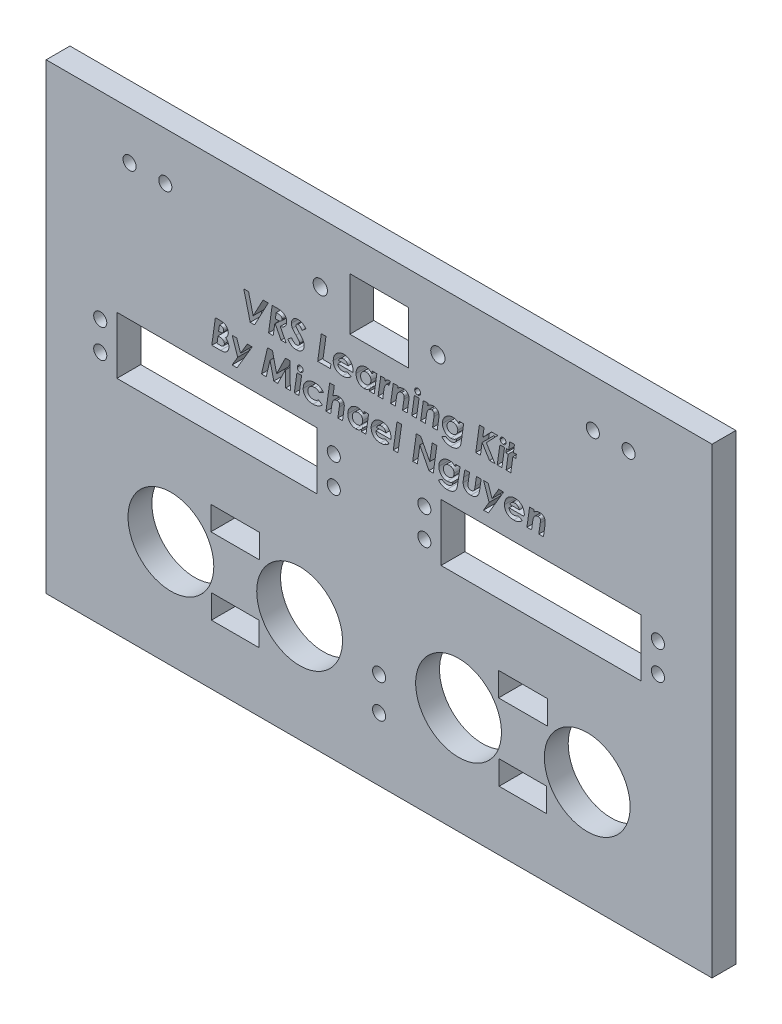
SolidWorks part; units mm, degrees
ref_plane "Front Plane" through (0, 0, 0) normal (0, 0, 1) x (1, 0, 0)
ref_plane "Top Plane" through (0, 0, 0) normal (0, 1, 0) x (1, 0, 0)
ref_plane "Right Plane" through (0, 0, 0) normal (1, 0, 0) x (0, 0, -1)
sketch "Sketch1" plane through (0, 0, 0) normal (0, 1, 0) x (1, 0, 0)
  line L1 (0, 0) -> (144.7, 0)
  line L2 (0, 0) -> (0, 5)
  line L3 (0, 5) -> (144.7, 5)
  line L4 (144.7, 0) -> (144.7, 5)
  dimension "D1" = 5
  dimension "D2" = 144.7
extrude "rearWall" add sketch "Sketch1" along normal blind 96.9847
ref_plane "referencePlane1" through (0, 91.9847, 0) normal (0, 1, 0) x (1, 0, 0)
sketch "Sketch12" plane through (0, 91.9847, 0) normal (0, 1, 0) x (1, 0, 0)
  line L0 (0, 0) -> (144.7, 0) construction
  line L1 (102.85, 0) -> (41.85, 0)
  line L2 (102.85, 0) -> (102.85, -24.75)
  line L3 (102.85, -24.75) -> (41.85, -24.75)
  line L4 (41.85, 0) -> (41.85, -24.75)
  point P4 (72.35, 0)
  point P7 (72.35, 0)
  dimension "D1" = 61
  dimension "D2" = 24.75
extrude "usbBracketBase" add sketch "Sketch12" against normal blind 16.75
sketch "Sketch13" plane through (0, 0, 24.75) normal (0, 0, 1) x (1, 0, 0)
  line L0 (72.35, 75.2347) -> (72.35, 91.9847) construction
  line L1 (41.85, 75.2347) -> (102.85, 75.2347) construction
  line L2 (20.7161, 91.9847) -> (-20.7161, 91.9847) construction
  line L3 (41.85, 75.2347) -> (41.85, 91.9847) construction
  line L4 (41.85, 90.2347) -> (49.85, 90.2347)
  line L5 (41.85, 90.2347) -> (41.85, 75.2347)
  line L6 (41.85, 75.2347) -> (49.85, 75.2347)
  line L7 (49.85, 90.2347) -> (49.85, 75.2347)
  line L8 (102.85, 75.2347) -> (94.85, 75.2347)
  line L9 (94.85, 90.2347) -> (94.85, 75.2347)
  line L10 (102.85, 90.2347) -> (94.85, 90.2347)
  line L11 (102.85, 90.2347) -> (102.85, 75.2347)
  dimension "D1" = 15
  dimension "D2" = 8
extrude "usbBracketTabs" cut sketch "Sketch13" against normal up to surface (24.75 mm away) up to face at (72.35, 83.6097, 0)
sketch "Sketch16" plane through (0, 0, 24.75) normal (0, 0, 1) x (1, 0, 0)
  line L0 (41.85, 91.9847) -> (102.85, 91.9847) construction
  line L1 (51.6, 76.9847) -> (93.1, 76.9847)
  line L2 (51.6, 76.9847) -> (51.6, 91.9847)
  line L3 (51.6, 91.9847) -> (93.1, 91.9847)
  line L4 (93.1, 76.9847) -> (93.1, 91.9847)
  point P4 (72.35, 91.9847)
  point P7 (72.35, 91.9847)
  dimension "D1" = 41.5
  dimension "D2" = 15
extrude "usbCavity" cut sketch "Sketch16" against normal up to surface (24.75 mm away) up to face at (72.35, 86.9222, 0)
sketch "Sketch17" plane through (0, 91.9847, 0) normal (0, 1, 0) x (1, 0, 0)
  line L0 (72.35, -24.75) -> (72.35, 0) construction
  line L1 (51.6, -24.75) -> (93.1, -24.75) construction
  line L2 (102.85, -12.375) -> (41.85, -12.375) construction
  line L3 (102.85, -24.75) -> (102.85, 0) construction
  line L4 (41.85, 0) -> (41.85, -24.75) construction
  line L5 (0, 0) -> (144.7, 0) construction
  line L6 (93.1, -24.75) -> (102.85, -24.75) construction
  circle A0 centre (98.85, -21.625) radius 1.375
  circle A1 centre (98.85, -3.125) radius 1.375
  circle A2 centre (45.85, -3.125) radius 1.375
  circle A3 centre (45.85, -21.625) radius 1.375
  dimension "D1" = 2.75
  dimension "D2" = 3.125
  dimension "D3" = 4
extrude "usbTopChassisMountingHoles" cut sketch "Sketch17" against normal blind 1.75
sketch "Sketch18" plane through (0, 0, 0) normal (0, 0, 1) x (1, 0, 0)
  line L0 (72.35, 76.9847) -> (72.35, 96.9847) construction
  line L1 (51.6, 76.9847) -> (93.1, 76.9847) construction
  line L2 (0, 96.9847) -> (144.7, 96.9847) construction
  line L3 (51.6, 91.9847) -> (51.6, 76.9847) construction
  circle A0 centre (60.015, 84.4847) radius 1.5
  circle A1 centre (84.685, 84.4847) radius 1.5
  dimension "D1" = 3
  dimension "D2" = 7.5
  dimension "D3" = 8.415
extrude "usbMountingHoles" cut sketch "Sketch18" against normal through all
sketch "Sketch19" plane through (0, 0, 0) normal (0, 0, 1) x (1, 0, 0)
  line L0 (72.35, 76.9847) -> (72.35, 78.9847) construction
  line L1 (66.225, 78.9847) -> (78.475, 78.9847)
  line L2 (66.225, 78.9847) -> (66.225, 89.9847)
  line L3 (66.225, 89.9847) -> (78.475, 89.9847)
  line L4 (78.475, 78.9847) -> (78.475, 89.9847)
  line L7 (51.6, 76.9847) -> (93.1, 76.9847) construction
  point P8 (72.35, 78.9847)
  dimension "D1" = 12.25
  dimension "D2" = 11
  dimension "D3" = 2
extrude "usbPortHole" cut sketch "Sketch19" against normal through all
sketch "Sketch20" plane through (0, 91.9847, 0) normal (0, 1, 0) x (1, 0, 0)
  line L0 (0, 0) -> (144.7, 0) construction
  line L5 (129.7, 0) -> (142.2, 0)
  line L6 (129.7, 0) -> (129.7, -17.135)
  line L7 (129.7, -17.135) -> (142.2, -17.135)
  line L8 (142.2, 0) -> (142.2, -17.135)
  line L9 (72.35, 5) -> (72.35, -24.75) construction
  line L10 (144.7, 5) -> (0, 5) construction
  line L11 (51.6, -24.75) -> (93.1, -24.75) construction
  line L12 (15, -17.135) -> (2.5, -17.135)
  line L13 (2.5, 0) -> (2.5, -17.135)
  line L14 (15, 0) -> (2.5, 0)
  line L15 (15, 0) -> (15, -17.135)
  dimension "D1" = 2.5
  dimension "D2" = 12.5
  dimension "D3" = 17.135
extrude "topChassisMountingTabs" add sketch "Sketch20" against normal blind 5
sketch "Sketch21" plane through (0, 91.9847, 0) normal (0, 1, 0) x (1, 0, 0)
  line L0 (142.2, -17.135) -> (142.2, 0) construction
  line L1 (142.2, 0) -> (129.7, 0) construction
  line L2 (72.35, 5) -> (72.35, -24.75) construction
  line L3 (144.7, 5) -> (0, 5) construction
  line L4 (51.6, -24.75) -> (93.1, -24.75) construction
  circle A0 centre (135.95, -8.5675) radius 1.375
  circle A1 centre (8.75, -8.5675) radius 1.375
  dimension "D1" = 2.75
  dimension "D2" = 6.25
  dimension "D3" = 8.5675
extrude "topChassisMountingHoles" cut sketch "Sketch21" against normal blind 5
ref_plane "referencePlane2" through (0, 7.5, 0) normal (0, -1, 0) x (-1, 0, 0)
sketch "bottomChassisReference" plane through (0, 0, -5) normal (0, 0, -1) x (-1, 0, 0)
  line L0 (-144.7, 0) -> (0, 0) construction
  line L1 (-142.2, 0) -> (-2.5, 0) construction
  line L2 (-142.2, 0) -> (-142.2, 7.5) construction
  line L3 (-142.2, 7.5) -> (-2.5, 7.5) construction
  line L4 (-2.5, 0) -> (-2.5, 7.5) construction
  point P6 (-72.35, 0)
  point P7 (-72.35, 0)
  dimension "D1" = 7.5
  dimension "D2" = 139.7
sketch "Sketch23" plane through (0, 7.5, 0) normal (0, -1, 0) x (-1, 0, 0)
  line L0 (-72.35, 0) -> (-72.35, -12.5) construction
  line L1 (0, 0) -> (-144.7, 0) construction
  line L3 (-15, 0) -> (-65, 0)
  line L4 (-15, 0) -> (-15, -12.5)
  line L5 (-15, -12.5) -> (-65, -12.5)
  line L6 (-65, 0) -> (-65, -12.5)
  line L7 (-129.7, -12.5) -> (-79.7, -12.5)
  line L8 (-79.7, 0) -> (-79.7, -12.5)
  line L9 (-129.7, 0) -> (-79.7, 0)
  line L10 (-129.7, 0) -> (-129.7, -12.5)
  dimension "D1" = 50
  dimension "D2" = 12.5
  dimension "D3" = 7.35
extrude "bottomChassisMountingTabs" add sketch "Sketch23" against normal blind 1.75
sketch "Sketch24" plane through (0, 7.5, 0) normal (0, -1, 0) x (1, 0, 0)
  line L0 (72.35, 0) -> (72.35, 12.5) construction
  line L1 (94.85, 0) -> (49.85, 0) construction
  line L2 (40, 0) -> (40, 12.5) construction
  line L3 (15, 0) -> (65, 0) construction
  line L4 (65, 12.5) -> (15, 12.5) construction
  line L5 (104.7, 12.5) -> (104.7, 0) construction
  line L6 (129.7, 12.5) -> (79.7, 12.5) construction
  line L7 (79.7, 0) -> (129.7, 0) construction
  line L8 (15, 12.5) -> (15, 0) construction
  circle A0 centre (18, 9.75) radius 1.375
  circle A1 centre (62, 9.75) radius 1.375
  circle A2 centre (126.7, 9.75) radius 1.375
  circle A3 centre (82.7, 9.75) radius 1.375
  dimension "D1" = 2.75
  dimension "D2" = 3
  dimension "D3" = 2.75
extrude "bottomChassisMountingHoles" cut sketch "Sketch24" against normal blind 10
sketch "Sketch25" plane through (0, 0, 0) normal (0, 0, 1) x (1, 0, 0)
  line L0 (72.35, 96.9847) -> (72.35, 0) construction
  line L1 (15, 9.25) -> (65, 9.25) construction
  line L2 (15, 9.25) -> (15, 37) construction
  line L3 (15, 37) -> (65, 37) construction
  line L4 (65, 9.25) -> (65, 37) construction
  line L5 (0, 96.9847) -> (144.7, 96.9847) construction
  line L6 (142.2, 0) -> (2.5, 0) construction
  line L7 (40, 9.25) -> (40, 37) construction
  line L8 (15, 23.125) -> (65, 23.125) construction
  circle A0 centre (26.5, 22.5) radius 9
  circle A1 centre (18.6693, 31.289) radius 0.875
  circle A3 centre (53.5, 22.5) radius 9
  circle A4 centre (61.3307, 31.289) radius 0.875
  circle A6 centre (18.6693, 13.711) radius 0.875
  circle A7 centre (61.3307, 13.711) radius 0.875
  circle A8 centre (126.0307, 31.289) radius 0.875
  circle A9 centre (126.0307, 13.711) radius 0.875
  circle A10 centre (83.3693, 13.711) radius 0.875
  circle A11 centre (83.3693, 31.289) radius 0.875
  circle A12 centre (91.2, 22.5) radius 9
  circle A13 centre (118.2, 22.5) radius 9
  dimension "D2" = 18
  dimension "D5" = 1.75
  dimension "D9" = 3.6693
  dimension "D1" = 27.75
  dimension "D3" = 13.25
  dimension "D4" = 11.5
  dimension "D6" = 5.711
  dimension "D7" = 3.6693
  dimension "D8" = 4.461
extrude "distanceSensorMountingHoles" cut sketch "Sketch25" against normal blind 10
sketch "Sketch26" plane through (0, 0, -5) normal (0, 0, -1) x (-1, 0, 0)
  line L0 (-72.35, 0) -> (-72.35, 96.9847) construction
  line L1 (-142.2, 0) -> (-2.5, 0) construction
  line L2 (-144.7, 96.9847) -> (0, 96.9847) construction
  line L3 (-144.7, 48.4923) -> (0, 48.4923) construction
  line L4 (-144.7, 96.9847) -> (-144.7, 0) construction
  line L5 (0, 96.9847) -> (0, 0) construction
  line L6 (-54.0762, 48.5554) -> (-26.8869, 61.234) construction
  line L11 (-26.8869, 61.234) -> (-22.6608, 52.1709) construction
  line L12 (-22.6608, 52.1709) -> (-49.85, 39.4923) construction
  line L13 (-49.85, 39.4923) -> (-54.0762, 48.5554) construction
  line L14 (-51.9631, 44.0239) -> (-24.7739, 56.7024) construction
  line L15 (-46.5252, 46.5596) -> (-43.9895, 41.1217) construction
  line L16 (-41.0874, 49.0953) -> (-38.5517, 43.6574) construction
  line L17 (-35.6496, 51.631) -> (-33.1138, 46.1931) construction
  line L18 (-30.2117, 54.1667) -> (-27.676, 48.7289) construction
  line L19 (-47.062, 47.7106) -> (-45.9885, 45.4086) construction
  line L20 (-45.2574, 43.8407) -> (-37.2036, 47.5962) construction
  line L21 (-23.3228, 60.6892) -> (-50.512, 48.0106) construction
  line L22 (-50.512, 48.0106) -> (-45.4406, 37.135) construction
  line L23 (-23.3228, 60.6892) -> (-18.2514, 49.8135) construction
  line L24 (-45.4406, 37.135) -> (-18.2514, 49.8135) construction
  line L25 (-40.0028, 39.6707) -> (-45.0742, 50.5464) construction
  line L26 (-23.3228, 60.6892) -> (-17.8849, 63.2249) construction
  line L27 (-17.8849, 63.2249) -> (-12.8135, 52.3492) construction
  line L28 (-18.2514, 49.8135) -> (-12.8135, 52.3492) construction
  line L29 (-45.4406, 37.135) -> (-50.8785, 34.5992) construction
  line L30 (-50.8785, 34.5992) -> (-55.9499, 45.4749) construction
  line L31 (-50.512, 48.0106) -> (-55.9499, 45.4749) construction
  circle A0 centre (-46.5252, 46.5596) radius 3 construction
  circle A1 centre (-41.0874, 49.0953) radius 3 construction
  circle A2 centre (-35.6496, 51.631) radius 3 construction
  circle A3 centre (-30.2117, 54.1667) radius 3 construction
  circle A4 centre (-43.9895, 41.1217) radius 3 construction
  circle A5 centre (-38.5517, 43.6574) radius 3 construction
  circle A6 centre (-33.1138, 46.1931) radius 3 construction
  circle A7 centre (-27.676, 48.7289) radius 3 construction
  circle A8 centre (-47.062, 47.7106) radius 0.575
  circle A9 centre (-45.9885, 45.4086) radius 0.575
  circle A10 centre (-41.6692, 50.3408) radius 0.575
  circle A11 centre (-40.5958, 48.0388) radius 0.575
  circle A12 centre (-36.2764, 52.971) radius 0.575
  circle A13 centre (-35.203, 50.669) radius 0.575
  circle A14 centre (-30.8837, 55.6013) radius 0.575
  circle A15 centre (-29.8102, 53.2992) radius 0.575
  circle A16 centre (-27.009, 47.292) radius 0.575
  circle A17 centre (-28.0824, 49.594) radius 0.575
  circle A18 centre (-33.5637, 47.1536) radius 0.575
  circle A19 centre (-32.4903, 44.8516) radius 0.575
  circle A20 centre (-37.9715, 42.4111) radius 0.575
  circle A21 centre (-39.045, 44.7132) radius 0.575
  circle A22 centre (-44.5263, 42.2727) radius 0.575
  circle A23 centre (-43.4528, 39.9707) radius 0.575
  circle A24 centre (-101.2472, 39.9707) radius 0.575
  circle A25 centre (-100.1737, 42.2727) radius 0.575
  circle A26 centre (-106.7285, 42.4111) radius 0.575
  circle A27 centre (-105.655, 44.7132) radius 0.575
  circle A28 centre (-112.2097, 44.8516) radius 0.575
  circle A29 centre (-111.1363, 47.1536) radius 0.575
  circle A30 centre (-117.691, 47.292) radius 0.575
  circle A31 centre (-116.6176, 49.594) radius 0.575
  circle A32 centre (-113.8163, 55.6013) radius 0.575
  circle A33 centre (-114.8898, 53.2992) radius 0.575
  circle A34 centre (-109.497, 50.669) radius 0.575
  circle A35 centre (-108.4236, 52.971) radius 0.575
  circle A36 centre (-103.0308, 50.3408) radius 0.575
  circle A37 centre (-104.1042, 48.0388) radius 0.575
  circle A38 centre (-98.7115, 45.4086) radius 0.575
  circle A39 centre (-97.638, 47.7106) radius 0.575
  circle A40 centre (-25.4458, 58.137) radius 0.575
  circle A41 centre (-24.3724, 55.835) radius 0.575
  circle A42 centre (-22.6446, 52.1297) radius 0.575
  circle A43 centre (-21.5711, 49.8277) radius 0.575
  circle A44 centre (-20.008, 60.6727) radius 0.575
  circle A45 centre (-18.9345, 58.3707) radius 0.575
  circle A46 centre (-17.2067, 54.6654) radius 0.575
  circle A47 centre (-16.1333, 52.3634) radius 0.575
  circle A56 centre (-128.5667, 52.3634) radius 0.575
  circle A57 centre (-124.692, 60.6727) radius 0.575
  circle A58 centre (-125.7655, 58.3707) radius 0.575
  circle A59 centre (-127.4933, 54.6654) radius 0.575
  circle A60 centre (-123.1289, 49.8277) radius 0.575
  circle A61 centre (-122.0554, 52.1297) radius 0.575
  circle A62 centre (-120.3276, 55.835) radius 0.575
  circle A63 centre (-119.2542, 58.137) radius 0.575
  circle A64 centre (-14.5701, 63.2084) radius 0.575 [skipped]
  circle A65 centre (-13.4967, 60.9064) radius 0.575 [skipped]
  circle A66 centre (-11.7689, 57.2011) radius 0.575 [skipped]
  circle A67 centre (-10.6955, 54.8991) radius 0.575 [skipped]
  circle A68 centre (-52.5515, 45.2887) radius 0.575
  circle A69 centre (-51.3724, 42.7601) radius 0.575
  circle A70 centre (-50.0169, 39.8503) radius 0.575
  circle A71 centre (-48.8366, 37.3223) radius 0.575
  circle A72 centre (-95.8634, 37.3223) radius 0.575
  circle A73 centre (-94.6831, 39.8503) radius 0.575
  circle A74 centre (-93.3276, 42.7601) radius 0.575
  circle A75 centre (-92.1485, 45.2887) radius 0.575
  circle A76 centre (-24.7739, 56.7024) radius 3 construction
  point P41 (-46.5252, 46.5596)
  dimension "D2" = 6
  dimension "D12" = 1.15
  dimension "D1" = 25
  dimension "D4" = 6
  dimension "D5" = 6
  dimension "D6" = 10
  dimension "D7" = 9
  dimension "D8" = 22.5
  dimension "D9" = 6
  dimension "D10" = 30
  dimension "D11" = 2.54
  dimension "D14" = 4
  dimension "D15" = 1.395
  dimension "D16" = 6
  dimension "D17" = 0.395
  dimension "D18" = 2.395
  dimension "D19" = 6
  dimension "D20" = 6
  dimension "D21" = 6
  dimension "D3" = 4
  dimension "D13" = 4
sketch "Sketch28" plane through (144.7, 0, 0) normal (1, 0, 0) x (0, 0, -1)
  line L4 (0, 0) -> (5, 0)
  line L5 (5, 0) -> (5, 96.9847)
  line L6 (5, 96.9847) -> (0, 96.9847)
  line L7 (0, 96.9847) -> (0, 0)
  line L8 (0, 0) -> (5, 0)
  line L9 (5, 0) -> (5, 96.9847)
  line L10 (5, 96.9847) -> (0, 96.9847)
  line L11 (0, 96.9847) -> (0, 0)
  dimension "D1" = 0
extrude "Boss-Extrude2" add sketch "Sketch28" along normal blind 2.5
sketch "Sketch29" plane through (0, 0, -5) normal (0, 0, -1) x (-1, 0, 0)
  line L0 (-72.35, 96.9847) -> (-72.35, 0) construction
  line L3 (-118.2, 22.5) -> (-109.2, 22.5) construction
  line L4 (-109.81, 28.5) -> (-99.59, 28.5)
  line L5 (-109.81, 28.5) -> (-109.81, 33.5)
  line L6 (-109.81, 33.5) -> (-99.59, 33.5)
  line L7 (-99.59, 28.5) -> (-99.59, 33.5)
  line L8 (-118.2, 22.5) -> (-118.2, 31.5) construction
  line L10 (-109.7, 12.5) -> (-99.7, 12.5)
  line L11 (-109.7, 12.5) -> (-109.7, 17.5)
  line L12 (-109.7, 17.5) -> (-99.7, 17.5)
  line L13 (-99.7, 12.5) -> (-99.7, 17.5)
  line L23 (-78.475, 89.9847) -> (-66.225, 89.9847) construction
  line L24 (-147.2, 96.9847) -> (0, 96.9847) construction
  line L25 (-147.2, 0) -> (0, 0) construction
  line L26 (-45, 12.5) -> (-45, 17.5)
  line L27 (-35, 12.5) -> (-45, 12.5)
  line L28 (-35, 12.5) -> (-35, 17.5)
  line L29 (-35, 17.5) -> (-45, 17.5)
  line L30 (-34.89, 28.5) -> (-34.89, 33.5)
  line L31 (-34.89, 28.5) -> (-45.11, 28.5)
  line L32 (-45.11, 28.5) -> (-45.11, 33.5)
  line L33 (-34.89, 33.5) -> (-45.11, 33.5)
  circle A0 centre (-118.2, 22.5) radius 9 construction
  circle A1 centre (-118.2, 22.5) radius 9 construction
  point P5 (-72.35, 89.9847)
  point P13 (-109.81, 31)
  point P20 (-109.7, 15)
  dimension "D1" = 5
  dimension "D2" = 10.22
  dimension "D3" = 8.5
  dimension "D4" = 8.39
  dimension "D5" = 10
  dimension "D6" = 5
  dimension "D7" = 5
  dimension "D8" = 8.5
extrude "Cut-Extrude1" cut sketch "Sketch29" against normal blind 10
sketch "Sketch30" plane through (0, 0, -5) normal (0, 0, -1) x (-1, 0, 0)
  line L0 (-73.6, 0) -> (-73.6, 96.9847) construction
  line L1 (-147.2, 0) -> (0, 0) construction
  line L2 (-147.2, 96.9847) -> (0, 96.9847) construction
  line L3 (-147.2, 0) -> (-73.6, 0) construction
  line L4 (-132.2, 42.4985) -> (-90.2, 42.4985)
  line L5 (-132.2, 42.4985) -> (-132.2, 54.4985)
  line L6 (-132.2, 54.4985) -> (-90.2, 54.4985)
  line L7 (-90.2, 42.4985) -> (-90.2, 54.4985)
  line L8 (-147.2, 0) -> (-147.2, 96.9847) construction
  line L9 (-99.59, 33.5) -> (-109.81, 33.5) construction
  line L10 (-15, 54.4985) -> (-57, 54.4985)
  line L11 (-57, 42.4985) -> (-57, 54.4985)
  line L12 (-15, 42.4985) -> (-57, 42.4985)
  line L13 (-15, 42.4985) -> (-15, 54.4985)
  dimension "D1" = 42
  dimension "D2" = 12
  dimension "D3" = 15
  dimension "D4" = 8.9985
extrude "Cut-Extrude2" cut sketch "Sketch30" against normal blind 10
sketch "Sketch31" plane through (0, 0, -5) normal (0, 0, -1) x (-1, 0, 0)
  line L0 (-111.2, 42.4985) -> (-111.2, 54.4985) construction
  line L1 (-132.2, 42.4985) -> (-90.2, 42.4985) construction
  line L2 (-90.2, 54.4985) -> (-132.2, 54.4985) construction
  line L3 (-90.2, 54.4985) -> (-83.2, 54.4985) construction
  line L4 (-132.2, 42.4985) -> (-139.2, 42.4985) construction
  line L6 (-132.2, 54.4985) -> (-139.2, 54.4985) construction
  line L7 (-139.2, 42.4985) -> (-139.2, 54.4985) construction
  line L8 (-83.2, 42.4985) -> (-83.2, 54.4985) construction
  line L9 (-90.2, 42.4985) -> (-83.2, 42.4985) construction
  line L10 (-90.2, 42.4985) -> (-90.2, 54.4985) construction
  line L11 (-73.6, 96.9847) -> (-73.6, 0) construction
  line L12 (-147.2, 96.9847) -> (0, 96.9847) construction
  line L13 (-147.2, 0) -> (0, 0) construction
  line L14 (-57, 42.4985) -> (-57, 54.4985) construction
  line L15 (-57, 42.4985) -> (-64, 42.4985) construction
  line L16 (-64, 42.4985) -> (-64, 54.4985) construction
  line L17 (-57, 54.4985) -> (-64, 54.4985) construction
  line L18 (-15, 54.4985) -> (-8, 54.4985) construction
  line L19 (-8, 42.4985) -> (-8, 54.4985) construction
  line L20 (-15, 42.4985) -> (-8, 42.4985) construction
  line L21 (-15, 42.4985) -> (-15, 54.4985) construction
  line L22 (-139.2, 48.4985) -> (-132.2, 48.4985) construction
  line L23 (-132.2, 42.4985) -> (-132.2, 48.4985) construction
  line L24 (-132.2, 54.4985) -> (-132.2, 42.4985) construction
  line L25 (-132.2, 48.4985) -> (-132.2, 54.4985) construction
  circle A0 centre (-135.7, 51.4985) radius 1.375
  circle A1 centre (-135.7, 45.4985) radius 1.375
  circle A2 centre (-86.7, 45.4985) radius 1.375
  circle A3 centre (-86.7, 51.4985) radius 1.375
  circle A4 centre (-60.5, 45.4985) radius 1.375
  circle A5 centre (-60.5, 51.4985) radius 1.375
  circle A6 centre (-11.5, 45.4985) radius 1.375
  circle A7 centre (-11.5, 51.4985) radius 1.375
  point P35 (-132.2, 51.4985)
  point P36 (-135.7, 48.4985)
  dimension "D2" = 2.75
  dimension "D1" = 7
extrude "Cut-Extrude3" cut sketch "Sketch31" against normal blind 10
sketch "Sketch32" plane through (0, 96.9847, 0) normal (0, 1, 0) x (1, 0, 0)
  line L0 (72.35, -24.75) -> (72.35, 5) construction
  line L1 (142.2, -17.135) -> (147.2, -17.135)
  line L2 (142.2, -17.135) -> (142.2, 5)
  line L3 (142.2, 5) -> (147.2, 5)
  line L4 (147.2, -17.135) -> (147.2, 5)
  line L7 (51.6, -24.75) -> (93.1, -24.75) construction
  line L8 (147.2, 5) -> (0, 5) construction
  line L9 (2.5, 5) -> (-2.5, 5)
  line L10 (-2.5, -17.135) -> (-2.5, 5)
  line L11 (2.5, -17.135) -> (-2.5, -17.135)
  line L12 (2.5, -17.135) -> (2.5, 5)
extrude "Cut-Extrude4" cut sketch "Sketch32" against normal through all
sketch "Sketch33" plane through (0, 0, -5) normal (0, 0, -1) x (-1, 0, 0)
  line L1 (-9.1526, 60.4475) -> (-139.9259, 60.4475)
  line L2 (-9.1526, 60.4475) -> (-9.1526, 10.7226)
  line L3 (-9.1526, 10.7226) -> (-139.9259, 10.7226)
  line L4 (-139.9259, 60.4475) -> (-139.9259, 10.7226)
extrude "Boss-Extrude3" add sketch "Sketch33" against normal up to surface (5 mm away) up to face at (59.125, 45.4985, 0)
sketch "Sketch34" plane through (0, 0, 0) normal (0, 0, 1) x (1, 0, 0)
  line L0 (72.35, 96.9847) -> (72.35, 0) construction
  line L1 (2.5, 96.9847) -> (142.2, 96.9847) construction
  line L2 (2.5, 0) -> (142.2, 0) construction
  line L4 (15, 9.25) -> (65, 9.25) construction
  line L7 (104.7, 9.25) -> (104.7, 42.4985) construction
  line L8 (129.7, 9.25) -> (79.7, 9.25) construction
  line L9 (132.2, 42.4985) -> (90.2, 42.4985) construction
  line L10 (15, 9.25) -> (65, 9.25) construction
  line L11 (15, 9.25) -> (15, 37) construction
  line L12 (15, 37) -> (65, 37) construction
  line L13 (65, 9.25) -> (65, 37) construction
  line L14 (65, 9.25) -> (65, 7.5) construction
  line L15 (40, 9.25) -> (40, 37) construction
  line L16 (109.81, 33.5) -> (99.59, 33.5)
  line L17 (34.89, 28.5) -> (45.11, 28.5)
  line L18 (34.89, 28.5) -> (34.89, 33.5)
  line L19 (34.89, 33.5) -> (45.11, 33.5)
  line L20 (45.11, 28.5) -> (45.11, 33.5)
  line L21 (35, 17.5) -> (45, 17.5)
  line L22 (35, 17.5) -> (35, 12.5)
  line L23 (35, 12.5) -> (45, 12.5)
  line L24 (45, 17.5) -> (45, 12.5)
  line L25 (99.59, 28.5) -> (99.59, 33.5)
  line L26 (109.81, 28.5) -> (99.59, 28.5)
  line L27 (109.81, 28.5) -> (109.81, 33.5)
  line L28 (109.7, 12.5) -> (99.7, 12.5)
  line L29 (99.7, 17.5) -> (99.7, 12.5)
  line L30 (109.7, 17.5) -> (99.7, 17.5)
  line L31 (109.7, 17.5) -> (109.7, 12.5)
  circle A2 centre (26.5, 22.5) radius 9
  circle A3 centre (53.5, 22.5) radius 9
  circle A4 centre (18.6693, 31.289) radius 0.875
  circle A5 centre (18.6693, 13.711) radius 0.875
  circle A6 centre (61.3307, 13.711) radius 0.875
  circle A7 centre (61.3307, 31.289) radius 0.875
  circle A8 centre (83.3693, 13.711) radius 0.875
  circle A9 centre (83.3693, 31.289) radius 0.875
  circle A10 centre (91.2, 22.5) radius 9
  circle A11 centre (118.2, 22.5) radius 9
  circle A12 centre (126.0307, 13.711) radius 0.875
  circle A13 centre (126.0307, 31.289) radius 0.875
  point P38 (40, 33.5)
  point P43 (40, 17.5)
  dimension "D3" = 18
  dimension "D6" = 1.75
  dimension "D1" = 50
  dimension "D2" = 27.75
  dimension "D4" = 11.5
  dimension "D5" = 14.5
  dimension "D7" = 3.6693
  dimension "D8" = 5.711
  dimension "D9" = 4.461
  dimension "D10" = 3.6693
  dimension "D11" = 10.22
  dimension "D12" = 5
  dimension "D13" = 3.5
  dimension "D14" = 5
  dimension "D15" = 10
  dimension "D16" = 3.25
extrude "Cut-Extrude5" cut sketch "Sketch34" against normal blind 10
sketch "Sketch35" plane through (0, 0, -5) normal (0, 0, -1) x (-1, 0, 0)
  line L0 (-72.35, 0) -> (-72.35, 96.9847) construction
  line L1 (-142.2, 0) -> (-2.5, 0) construction
  line L2 (-142.2, 96.9847) -> (-2.5, 96.9847) construction
  line L3 (-59.35, 46.5252) -> (-59.35, 52.5252) construction
  line L4 (-66.35, 58.5252) -> (-10.35, 58.5252) construction
  line L5 (-66.35, 58.5252) -> (-66.35, 46.5252) construction
  line L6 (-66.35, 46.5252) -> (-10.35, 46.5252) construction
  line L7 (-10.35, 58.5252) -> (-10.35, 46.5252) construction
  line L8 (-38.35, 46.5252) -> (-38.35, 58.5252) construction
  line L9 (-59.35, 52.5252) -> (-66.35, 52.5252) construction
  line L10 (-59.35, 52.5252) -> (-59.35, 58.5252) construction
  line L12 (-85.35, 46.5252) -> (-127.35, 46.5252)
  line L13 (-59.35, 58.5252) -> (-17.35, 58.5252)
  line L14 (-59.35, 58.5252) -> (-59.35, 46.5252)
  line L15 (-59.35, 46.5252) -> (-17.35, 46.5252)
  line L16 (-17.35, 58.5252) -> (-17.35, 46.5252)
  line L17 (-127.35, 58.5252) -> (-127.35, 46.5252)
  line L18 (-85.35, 58.5252) -> (-127.35, 58.5252)
  line L19 (-85.35, 58.5252) -> (-85.35, 46.5252)
  line L20 (-85.35, 52.5252) -> (-59.35, 52.5252) construction
  circle A0 centre (-62.85, 55.5252) radius 1.375
  circle A1 centre (-62.85, 49.5252) radius 1.375
  circle A2 centre (-13.85, 49.5252) radius 1.375
  circle A3 centre (-13.85, 55.5252) radius 1.375
  circle A4 centre (-130.85, 55.5252) radius 1.375
  circle A5 centre (-130.85, 49.5252) radius 1.375
  circle A6 centre (-81.85, 49.5252) radius 1.375
  circle A7 centre (-81.85, 55.5252) radius 1.375
  point P11 (-62.85, 52.5252)
  point P19 (-59.35, 55.5252)
  point P28 (-85.35, 52.5252)
  point P44 (-72.35, 52.5252)
  dimension "D4" = 2.75
  dimension "D1" = 56
  dimension "D2" = 12
  dimension "D3" = 7
  dimension "D5" = 39.0252
  dimension "D6" = 26
  dimension "D7" = 7
extrude "Cut-Extrude6" cut sketch "Sketch35" against normal blind 10
sketch "Sketch36" plane through (0, 0, -5) normal (0, 0, -1) x (-1, 0, 0)
  line L0 (-72.35, 0) -> (-72.35, 96.9847) construction
  line L1 (-142.2, 0) -> (-2.5, 0) construction
  line L2 (-142.2, 96.9847) -> (-2.5, 96.9847) construction
  circle A0 centre (-126.0307, 31.289) radius 1.25
  circle A1 centre (-126.0307, 13.711) radius 1.25
  circle A2 centre (-83.3693, 31.289) radius 1.25
  circle A3 centre (-83.3693, 13.711) radius 1.25
  circle A4 centre (-18.6693, 13.711) radius 1.25
  circle A5 centre (-61.3307, 13.711) radius 1.25
  circle A6 centre (-61.3307, 31.289) radius 1.25
  circle A7 centre (-18.6693, 31.289) radius 1.25
  dimension "D1" = 2.5
extrude "Cut-Extrude7" cut sketch "Sketch36" against normal offset from surface (4 mm away) 1 up to face at (61.475, 55.5252, 0)
sketch "Sketch37" plane through (0, 91.9847, 0) normal (0, 1, 0) x (1, 0, 0)
  line L1 (102.85, -24.75) -> (41.85, -24.75)
  line L2 (102.85, -24.75) -> (102.85, 0)
  line L3 (102.85, 0) -> (41.85, 0)
  line L4 (41.85, -24.75) -> (41.85, 0)
extrude "Cut-Extrude8" cut sketch "Sketch37" against normal up to surface (16.75 mm away) up to face at (72.35, 75.2347, 12.375)
sketch "Sketch38" plane through (0, 91.9847, 0) normal (0, 1, 0) x (1, 0, 0)
  line L1 (142.2, -17.135) -> (2.5, -17.135)
  line L2 (142.2, -17.135) -> (142.2, 0)
  line L3 (142.2, 0) -> (2.5, 0)
  line L4 (2.5, -17.135) -> (2.5, 0)
extrude "Cut-Extrude9" cut sketch "Sketch38" against normal blind 10
sketch "Sketch39" plane through (0, 0, 0) normal (0, 0, 1) x (1, 0, 0)
  line L0 (9, 24.25) -> (15, 24.25) construction
  line L1 (65, 9.25) -> (79.7, 9.25) construction
  line L2 (65, 9.25) -> (65, 7.5) construction
  line L3 (65, 7.5) -> (79.7, 7.5) construction
  line L4 (79.7, 9.25) -> (79.7, 7.5) construction
  line L5 (69.35, 24.25) -> (75.35, 24.25) construction
  line L6 (69.35, 24.25) -> (69.35, 9.25) construction
  line L7 (69.35, 9.25) -> (75.35, 9.25) construction
  line L8 (75.35, 24.25) -> (75.35, 9.25) construction
  line L9 (9, 24.25) -> (9, 9.25) construction
  line L10 (9, 9.25) -> (15, 9.25) construction
  line L11 (15, 24.25) -> (15, 9.25) construction
  line L12 (129.7, 24.25) -> (135.7, 24.25) construction
  line L13 (129.7, 24.25) -> (129.7, 9.25) construction
  line L14 (129.7, 9.25) -> (135.7, 9.25) construction
  line L15 (135.7, 24.25) -> (135.7, 9.25) construction
  line L16 (72.35, 7.5) -> (72.35, 9.25) construction
  circle A0 centre (72.35, 20.25) radius 1.375
  circle A1 centre (72.35, 13.25) radius 1.375
  circle A2 centre (12, 20.25) radius 1.375
  circle A3 centre (12, 13.25) radius 1.375
  circle A4 centre (132.7, 13.25) radius 1.375
  circle A5 centre (132.7, 20.25) radius 1.375
  point P21 (72.35, 9.25)
  point P22 (72.35, 9.25)
  point P32 (12, 9.25)
  dimension "D3" = 2.75
  dimension "D1" = 6
  dimension "D2" = 15
  dimension "D4" = 4
  dimension "D5" = 7
extrude "Cut-Extrude10" cut sketch "Sketch39" against normal blind 10
sketch "Sketch40" plane through (0, 9.25, 0) normal (0, 1, 0) x (1, 0, 0)
  line L1 (15, -12.5) -> (129.7, -12.5)
  line L2 (15, -12.5) -> (15, 0)
  line L3 (15, 0) -> (129.7, 0)
  line L4 (129.7, -12.5) -> (129.7, 0)
extrude "Cut-Extrude11" cut sketch "Sketch40" against normal blind 10
sketch "Sketch41" plane through (0, 0, 0) normal (0, 0, 1) x (1, 0, 0)
  line L0 (2.5, 96.9847) -> (142.2, 96.9847) construction
  line L1 (2.5, 96.9847) -> (2.5, 0) construction
  line L2 (72.35, 0) -> (72.35, 96.9847) construction
  line L3 (2.5, 0) -> (142.2, 0) construction
  circle A0 centre (20, 87) radius 1.375
  circle A1 centre (27.5, 87) radius 1.375
  circle A2 centre (117.2, 87) radius 1.375
  circle A3 centre (124.7, 87) radius 1.375
  dimension "D1" = 2.75
  dimension "D2" = 9.9847
  dimension "D3" = 17.5
  dimension "D4" = 7.5
extrude "Cut-Extrude12" cut sketch "Sketch41" against normal blind 10
sketch "Sketch42" plane through (0, 0, -5) normal (0, 0, -1) x (-1, 0, 0)
  line L0 (-102.525, 12.5) -> (-102.525, 32.5) construction
  line L1 (-125.025, 12.5) -> (-80.025, 12.5) construction
  line L2 (-125.025, 12.5) -> (-125.025, 32.5) construction
  line L3 (-125.025, 32.5) -> (-80.025, 32.5) construction
  line L4 (-80.025, 12.5) -> (-80.025, 32.5) construction
  line L5 (-107.635, 33.5) -> (-97.415, 33.5)
  line L6 (-107.635, 33.5) -> (-107.635, 28.5)
  line L7 (-107.635, 28.5) -> (-97.415, 28.5)
  line L8 (-97.415, 33.5) -> (-97.415, 28.5)
  line L9 (-132.7, 13.25) -> (-72.35, 13.25) construction
  line L10 (-102.525, 13.25) -> (-102.525, 0) construction
  line L11 (-142.2, 0) -> (-2.5, 0) construction
  line L12 (-72.35, 96.9847) -> (-72.35, 0) construction
  line L13 (-142.2, 96.9847) -> (-2.5, 96.9847) construction
  line L14 (-37.175, 12.5) -> (-47.175, 12.5)
  line L15 (-107.525, 17.5) -> (-97.525, 17.5)
  line L16 (-107.525, 17.5) -> (-107.525, 12.5)
  line L17 (-107.525, 12.5) -> (-97.525, 12.5)
  line L18 (-97.525, 17.5) -> (-97.525, 12.5)
  line L19 (-47.175, 17.5) -> (-47.175, 12.5)
  line L20 (-37.175, 17.5) -> (-47.175, 17.5)
  line L21 (-37.175, 17.5) -> (-37.175, 12.5)
  line L22 (-37.065, 28.5) -> (-47.285, 28.5)
  line L23 (-47.285, 33.5) -> (-47.285, 28.5)
  line L24 (-37.065, 33.5) -> (-47.285, 33.5)
  line L25 (-37.065, 33.5) -> (-37.065, 28.5)
  line L26 (-19.675, 12.5) -> (-64.675, 12.5) construction
  line L27 (-19.675, 12.5) -> (-19.675, 32.5) construction
  line L28 (-19.675, 32.5) -> (-64.675, 32.5) construction
  line L29 (-64.675, 12.5) -> (-64.675, 32.5) construction
  circle A0 centre (-116.025, 22.5) radius 9
  circle A2 centre (-89.025, 22.5) radius 9
  circle A3 centre (-118.2, 22.5) radius 9 construction
  circle A5 centre (-118.2, 22.5) radius 9 construction
  circle A6 centre (-55.675, 22.5) radius 9
  circle A7 centre (-28.675, 22.5) radius 9
  dimension "D3" = 18
  dimension "D1" = 45
  dimension "D2" = 20
  dimension "D4" = 10
  dimension "D5" = 9
  dimension "D6" = 10.22
  dimension "D7" = 5
  dimension "D8" = 6
  dimension "D9" = 8.39
  dimension "D10" = 5
  dimension "D11" = 10
  dimension "D12" = 8.5
  dimension "D13" = 5
sketch "Sketch43" plane through (0, 0, -5) normal (0, 0, -1) x (-1, 0, 0)
  line L1 (-128.2939, 36.5996) -> (-78.4695, 36.5996)
  line L2 (-128.2939, 36.5996) -> (-128.2939, 8.0313)
  line L3 (-128.2939, 8.0313) -> (-78.4695, 8.0313)
  line L4 (-78.4695, 36.5996) -> (-78.4695, 8.0313)
  line L5 (-66.4853, 36.5996) -> (-14.8298, 36.5996)
  line L6 (-66.4853, 36.5996) -> (-66.4853, 5.1908)
  line L7 (-66.4853, 5.1908) -> (-14.8298, 5.1908)
  line L8 (-14.8298, 36.5996) -> (-14.8298, 5.1908)
extrude "Boss-Extrude4" add sketch "Sketch43" against normal up to surface (5 mm away) up to face at (21.375, 87, 0)
extrude "Cut-Extrude13" cut sketch "Sketch42" against normal through all both and the other way through all
sketch "Sketch44" plane through (0, 0, 0) normal (0, 0, 1) x (1, 0, 0)
  circle A0 centre (132.7, 13.25) radius 1.375 construction
  circle A1 centre (132.7, 20.25) radius 1.375 construction
  circle A4 centre (12, 13.25) radius 1.375 construction
  circle A5 centre (12, 20.25) radius 1.375 construction
  circle A6 centre (132.7, 13.25) radius 1.375
  circle A7 centre (132.7, 20.25) radius 1.375
  circle A10 centre (12, 13.25) radius 1.375
  circle A11 centre (12, 20.25) radius 1.375
extrude "Boss-Extrude5" add sketch "Sketch44" against normal up to surface (5 mm away) up to face at (64.675, 22.5, -5)
sketch "Sketch46" plane through (0, 0, 0) normal (0, 0, 1) x (1, 0, 0)
  line L0 (31.6367, 62.4848) -> (31.6367, 76.5595) construction
  line L2 (40.2134, 70.6848) -> (104.4866, 70.6848) construction
  line L3 (31.6367, 62.4848) -> (113.0633, 62.4848) construction
  line L6 (31.6367, 76.5595) -> (113.0633, 76.5595) construction
  line L7 (113.0633, 76.5595) -> (113.0633, 62.4848) construction
  line L8 (31.6367, 62.4848) -> (31.6367, 60.9504) construction
  line L9 (31.6367, 60.9504) -> (113.0633, 60.9504) construction
  line L10 (113.0633, 60.9504) -> (113.0633, 62.4848) construction
  line L11 (72.35, 76.5595) -> (72.35, 60.9504) construction
  line L12 (66.225, 78.9847) -> (78.475, 78.9847) construction
  text T0 "VRS Learning Kit" font "Century Gothic" height 5.4
  text T1 "By Michael Nguyen" font "Century Gothic" height 5.4
  point P12 (72.35, 68.7549)
  point P15 (72.35, 70.6848)
  point P16 (72.35, 62.4848)
  dimension "D1" = 8.2
  dimension "D2" = 1.5344
  dimension "D3" = 15.6091
  dimension "D4" = 81.4266
  dimension "D5" = 10.2297
extrude "Cut-Extrude15" cut sketch "Sketch46" against normal blind 2.5 and the other way through all
